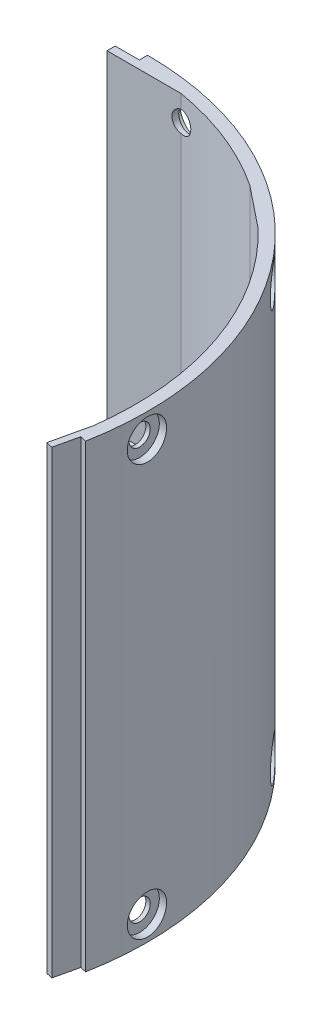
SolidWorks part; units mm, degrees
ref_plane "Спереди" through (0, 0, 0) normal (0, 0, 1) x (1, 0, 0)
ref_plane "Сверху" through (0, 0, 0) normal (0, 1, 0) x (1, 0, 0)
ref_plane "Справа" through (0, 0, 0) normal (1, 0, 0) x (0, 0, -1)
sketch "Эскиз2" plane through (0, 0, 0) normal (0, 1, 0) x (1, 0, 0)
  line L0 (0, -1000) -> (0, 49000) construction
  line L1 (-8.2529, 48.3) -> (8.2529, 48.3) construction
  line L2 (33.9524, 35.3303) -> (27.0476, 40.8587) construction
  line L3 (48.5627, -6.5315) -> (46.5973, -15.1557) construction
  line L4 (-4, 48.3) -> (8.2529, 48.3)
  line L5 (33.9524, 35.3303) -> (27.0476, 40.8587)
  line L6 (48.5627, -6.5315) -> (46.5973, -15.1557) construction
  line L7 (-4, 48.3) -> (-4, 49.65)
  line L8 (-4, 49.65) -> (0, 49.65)
  line L10 (-8.2529, 48.3) -> (-4, 48.3) construction
  line L12 (0, 0) -> (47.58, -10.8436) construction
  line L13 (50.1312, -9.3737) -> (49.0969, -9.138)
  line L14 (49.0969, -9.138) -> (48.2081, -13.038)
  line L15 (48.2081, -13.038) -> (47.1356, -12.7936)
  line L16 (47.58, -10.8436) -> (49.725, -11.3324) construction
  line L17 (47.1356, -12.7936) -> (48.5627, -6.5315)
  line L19 (0, 49.65) -> (0, 51)
  line L20 (0, 48.3) -> (0, 49.65) construction
  circle A0 centre (0, 0) radius 51 construction
  arc A1 (50.1312, -9.3737) -> (0, 51) centre (0, 0) ccw
  circle A2 centre (0, 0) radius 51 construction
  arc A3 (48.5627, -6.5315) -> (33.9524, 35.3303) centre (0, 0) ccw construction
  arc A4 (0, 51) -> (0, -51) centre (0, 0) ccw construction
  arc A5 (48.5627, -6.5315) -> (33.9524, 35.3303) centre (0, 0) ccw
  arc A6 (8.2529, 48.3) -> (27.0476, 40.8587) centre (0, 0) cw
  arc A7 (0, -51) -> (49.725, -11.3324) centre (0, 0) ccw construction
  arc A8 (49.725, -11.3324) -> (50.1312, -9.3737) centre (0, 0) ccw construction
  point P25 (48.6525, -11.088)
  dimension "D1" = 4
extrude "Бобышка-Вытянуть2" add sketch "Эскиз2" along normal up to surface (76 mm away)
ref_plane "Плоскость4" through (12.7171, 0, -36.1271) normal (-0.332, 0, 0.9433) x (0.9433, 0, 0.332)
sketch "Эскиз7" plane through (12.7171, 0, -36.1271) normal (-0.332, 0, 0.9433) x (0.9433, 0, 0.332)
  line L5 (-8.2529, 17) -> (5.2529, 17) construction
  line L6 (-8.2529, 17) -> (5.2529, 17) construction
  line L7 (8.2529, 14) -> (5.2529, 17) construction
  line L8 (8.2529, 14) -> (5.2529, 17)
  line L9 (-8.2529, 0) -> (8.2529, 0) construction
  line L16 (-8.2529, 0) -> (8.2529, 0)
  line L17 (-8.2529, 76) -> (-8.2529, 0) construction
  line L18 (-8.2529, 17) -> (-8.2529, 0) construction
  line L19 (8.7529, 14.2071) -> (8.7529, 0)
  line L20 (8.7529, 14.2071) -> (5.46, 17.5)
  line L21 (8.2529, 14) -> (8.2529, 0) construction
  line L22 (8.2529, 14) -> (8.2529, 0) construction
  line L23 (-8.7529, 17.5) -> (5.46, 17.5)
  line L24 (-8.7529, 17.5) -> (-8.7529, 0)
  line L25 (-8.7529, 0) -> (-8.2529, 0)
  line L26 (8.2529, 0) -> (8.7529, 0)
  dimension "D1" = 0.5
extrude "Вырез-Вытянуть3" cut sketch "Эскиз7" against normal through all contours L16 L26 L19 L20 L23 L24 L25 region at (12.587, 8.6121, -36.1729)
sketch "Эскиз9" plane through (0, 0, -48.3) normal (0, 0, 1) x (1, 0, 0)
  line L4 (8.7529, 0) -> (8.7529, 17.5)
  line L6 (-4, 76) -> (-4, 0) construction
  line L7 (-4, 19.5) -> (-4, 0)
  line L8 (-4, 76) -> (-4, 19.5) construction
  line L9 (-4, 19.5) -> (-6.5, 17) construction
  line L10 (-8.2529, 0) -> (-4, 0) construction
  line L11 (8.7529, 17.5) -> (6.7071, 17.5)
  line L12 (6.7071, 17.5) -> (3.7071, 20.5)
  line L13 (3.7071, 20.5) -> (-3.7071, 20.5)
  line L14 (-8.2529, 0) -> (8.2529, 0)
  line L15 (8.2529, 0) -> (8.2529, 17)
  line L24 (8.2529, 17) -> (6.5, 17)
  line L25 (6.5, 17) -> (3.5, 20)
  line L26 (3.5, 20) -> (-3.5, 20)
  line L28 (-3.7071, 20.5) -> (-4, 20.2071)
  line L29 (-3.5, 20) -> (-6.5, 17)
  line L30 (-6.5, 17) -> (-8.2529, 17)
  line L31 (-8.2529, 17) -> (-8.2529, 0)
  line L32 (-4, 0) -> (8.2529, 0)
  line L33 (8.2529, 0) -> (8.2529, 17) construction
  line L34 (8.2529, 17) -> (6.5, 17) construction
  line L35 (6.5, 17) -> (3.5, 20) construction
  line L36 (3.5, 20) -> (-3.5, 20) construction
  line L37 (-3.5, 20) -> (-4, 19.5)
  line L38 (-6.5, 17) -> (-8.2529, 17) construction
  line L39 (-8.2529, 17) -> (-8.2529, 0) construction
  line L40 (-4, 19.5) -> (-4, 20.2071)
  line L41 (-4, 20.2071) -> (-4.3536, 19.8536) construction
  line L42 (-3.7071, 20.5) -> (-4.3536, 19.8536) construction
  line L43 (8.7529, 0) -> (8.2529, 0)
  line M9 (-8.2529, 0) -> (8.2529, 0)
  line M10 (8.2529, 0) -> (8.2529, 17)
  line M11 (8.2529, 17) -> (6.5, 17)
  line M12 (6.5, 17) -> (3.5, 20)
  line M13 (3.5, 20) -> (-3.5, 20)
  line M14 (-3.5, 20) -> (-6.5, 17)
  dimension "D1" = 0
  dimension "D2" = 0.5
extrude "Вырез-Вытянуть4" cut sketch "Эскиз9" against normal through all contours L7 M14 M9 M10 M11 M12 M13 | L43 L4 L11 L12 L13 L28 L40 M14 M13 M12 M11 M10 region at (8.5029, 0.2414, -48.3) region at (1.9477, 9.6325, -48.3)
sketch "Эскиз10" plane through (0, 12, 0) normal (0, 1, 0) x (1, 0, 0)
  line L0 (-4, 48.3) -> (8.2529, 48.3) construction
  line L1 (-4, 48.3) -> (8.2529, 48.3)
  line L2 (23.8222, 42.8194) -> (20.9924, 43.8155) construction
  line L3 (8.2529, 48.3) -> (20.9924, 43.8155) construction
  line L4 (23.8222, 42.8194) -> (20.9924, 43.8155)
  line L5 (8.2529, 48.3) -> (20.9924, 43.8155)
  line L7 (23.4097, 41.9045) -> (20.6603, 42.8723)
  line L8 (8.082, 47.3) -> (20.6603, 42.8723)
  line L9 (-4, 47.3) -> (8.082, 47.3)
  line L10 (-4, 47.3) -> (-4, 48.3)
  line L11 (26.4956, 40.0248) -> (27.0476, 40.8587) construction
  line L12 (26.4956, 40.0248) -> (28.4646, 39.7241)
  line L13 (27.0476, 40.8587) -> (33.9524, 35.3303) construction
  line L14 (28.4646, 39.7241) -> (27.0476, 40.8587) construction
  line L15 (28.4646, 39.7241) -> (27.0476, 40.8587) construction
  line L16 (28.4646, 39.7241) -> (27.0476, 40.8587)
  arc A0 (27.0476, 40.8587) -> (8.2529, 48.3) centre (0, 0) ccw construction
  arc A1 (27.0476, 40.8587) -> (23.8222, 42.8194) centre (0, 0) ccw
  arc A2 (23.8222, 42.8194) -> (8.2529, 48.3) centre (0, 0) ccw construction
  arc A3 (26.4956, 40.0248) -> (23.4097, 41.9045) centre (0, 0) ccw
  dimension "D2" = 30
  dimension "D1" = 1
extrude "Бобышка-Вытянуть7" add sketch "Эскиз10" along normal blind 10
sketch "Эскиз13" plane through (0, 22, 0) normal (0, 1, 0) x (1, 0, 0)
  line L0 (23.8222, 42.8194) -> (8.2529, 48.3) construction
  line L1 (23.8222, 42.8194) -> (8.2529, 48.3)
  arc A0 (27.0476, 40.8587) -> (8.2529, 48.3) centre (0, 0) ccw construction
  arc A1 (27.0476, 40.8587) -> (8.2529, 48.3) centre (0, 0) ccw
  line M2 (23.8222, 42.8194) -> (8.2529, 48.3)
extrude "Бобышка-Вытянуть8" add sketch "Эскиз13" against normal up to surface (4.5 mm away) contours A1 M2 region at (16.1306, 22, -45.824) up to face at (13.0597, 17.5, -47.6707)
sketch "Эскиз14" plane through (0, 17.5, 0) normal (0, -1, 0) x (1, 0, 0)
  line L0 (21.3189, -44.1192) -> (21.1877, -43.7468)
  line L1 (21.1877, -43.7468) -> (8.2529, -48.3) construction
  line L4 (21.9869, -46.0171) -> (21.3189, -44.1192)
  line L5 (23.8222, -42.8194) -> (8.2529, -48.3)
  line L6 (8.2529, -48.3) -> (6.7071, -48.3)
  line L7 (6.7071, -48.3) -> (6.7071, -50.557)
  line L8 (21.9869, -46.0171) -> (21.3189, -44.1192)
  line L9 (23.8222, -42.8194) -> (21.1877, -43.7468)
  line L10 (8.2529, -48.3) -> (6.7071, -48.3) construction
  line L11 (6.7071, -48.3) -> (6.7071, -50.557) construction
  arc A2 (6.7071, -50.557) -> (21.9869, -46.0171) centre (0, 0) ccw
  arc A3 (21.3189, -44.1192) -> (23.8222, -42.8194) centre (0, 0) ccw
  arc A4 (6.7071, -50.557) -> (21.9869, -46.0171) centre (0, 0) ccw construction
  arc A5 (21.3189, -44.1192) -> (23.8222, -42.8194) centre (0, 0) ccw
  dimension "D1" = 0
extrude "Бобышка-Вытянуть9" add sketch "Эскиз14" along normal up to surface contours A5 L9 L0 up to face at (23.2708, 15.6229, -44.011)
chamfer "Фаска1" distance 1 angle 45 4 edges at (2.041, 22, -47.3) (15.7459, 22, -44.6022) (24.9703, 22, -40.9937) (27.4801, 22, -39.8745)
ref_plane "Плоскость5" through (51, 0, 0) normal (1, 0, 0) x (0, 0, -1)
sketch "Эскиз15" plane through (51, 0, 0) normal (1, 0, 0) x (0, 0, -1)
  line L0 (0, -1000) -> (0, 49000) construction
  circle A0 centre (0, 4) radius 3.25
  dimension "D1" = 6.5
  dimension "D2" = 4
extrude "Вырез-Вытянуть5" cut sketch "Эскиз15" against normal blind 1.3
sketch "Эскиз16" plane through (49.7, 0, 0) normal (1, 0, 0) x (0, 0, -1)
  circle A0 centre (0, 4) radius 3.25 construction
  circle A1 centre (0, 4) radius 3.25 construction
  circle A2 centre (0, 4) radius 1.75
  dimension "D1" = 3.5
extrude "Вырез-Вытянуть6" cut sketch "Эскиз16" against normal through all
pattern_circular "Круговой массив3" count 3 every 20 about axis through (0, 0, 0) along (0, 1, 0) skipping 1 of "Вырез-Вытянуть5", "Вырез-Вытянуть6"
sketch "Эскиз17" plane through (51, 0, 0) normal (1, 0, 0) x (0, 0, -1)
  line L0 (0, -1000) -> (0, 49000) construction
  line L1 (51, 76) -> (-9.3737, 76) construction
  circle A0 centre (0, 72) radius 3.25
  circle A1 centre (0, 4) radius 3.25 construction
  dimension "D1" = 4
extrude "Вырез-Вытянуть7" cut sketch "Эскиз17" against normal blind 1.3
sketch "Эскиз18" plane through (49.7, 0, 0) normal (1, 0, 0) x (0, 0, -1)
  circle A0 centre (0, 72) radius 3.25 construction
  circle A1 centre (0, 72) radius 3.25 construction
  circle A2 centre (0, 72) radius 1.75
  circle A3 centre (0, 4) radius 1.75 construction
extrude "Вырез-Вытянуть8" cut sketch "Эскиз18" against normal through all
pattern_circular "Круговой массив5" count 5 every 20 about axis through (0, 76, 0) along (0, 1, 0) skipping 1, 3 of "Вырез-Вытянуть8", "Вырез-Вытянуть7"
